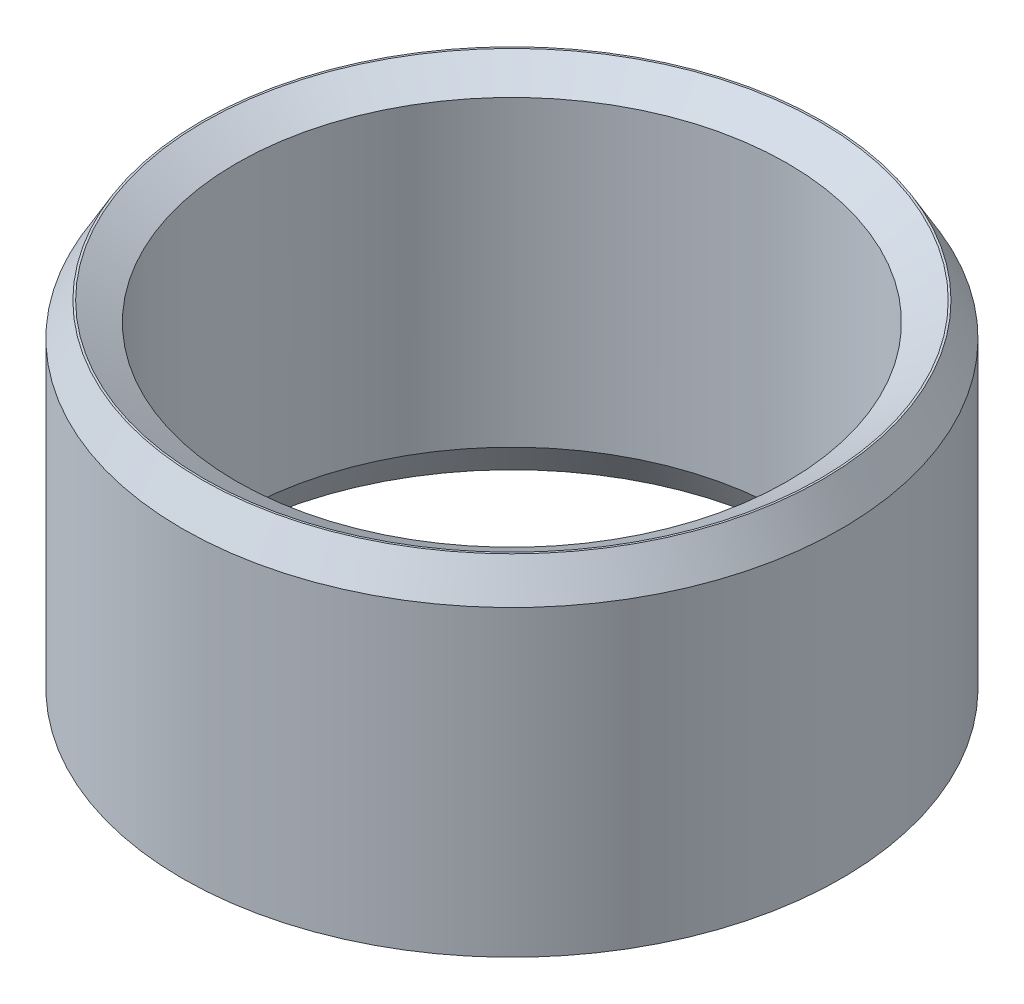
SolidWorks part; units mm, degrees
ref_plane "Front Plane" through (0, 0, 0) normal (0, 0, 1) x (1, 0, 0)
ref_plane "Top Plane" through (0, 0, 0) normal (0, 1, 0) x (1, 0, 0)
ref_plane "Right Plane" through (0, 0, 0) normal (1, 0, 0) x (0, 0, -1)
sketch "Sketch1" plane through (0, 0, 0) normal (0, 1, 0) x (1, 0, 0)
  circle A0 centre (0, 0) radius 35
  dimension "SLEEVE_OD" = 70
extrude "Boss-Extrude1" add sketch "Sketch1" along normal blind 37.7038
sketch "Sketch2" plane through (0, 0, 0) normal (0, 1, 0) x (1, 0, 0)
  circle A0 centre (0, 0) radius 29.2544
  dimension "BORE_D" = 58.5088
extrude "Cut-Extrude1" cut sketch "Sketch2" along normal through all
chamfer "Chamfer1" distance 3.5107 angle 30 4 edges at (0, 37.7038, 29.2544) (0, 0, 29.2544) (0, 0, 35) (0, 37.7038, 35) first distance on face at (0, 37.7038, 29.2544) first distance on face at (0, 0, 29.2544) first distance on face at (0, 37.7038, 35)
